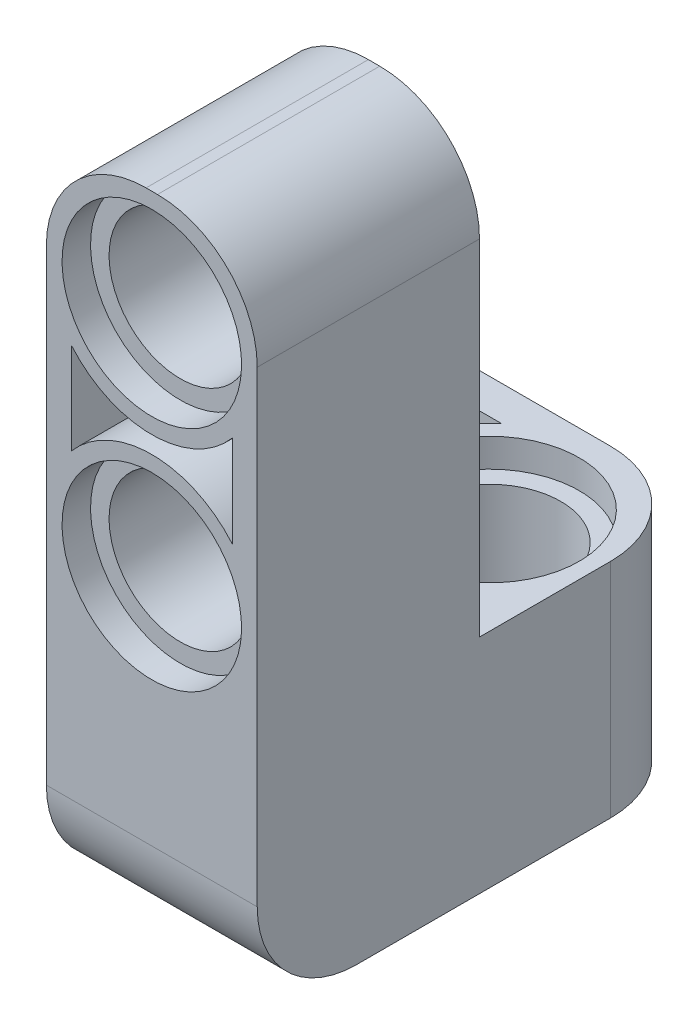
SolidWorks part; units mm, degrees
ref_plane "前视基准面" through (0, 0, 0) normal (0, 0, 1) x (1, 0, 0)
ref_plane "上视基准面" through (0, 0, 0) normal (0, 1, 0) x (1, 0, 0)
ref_plane "右视基准面" through (0, 0, 0) normal (1, 0, 0) x (0, 0, -1)
other "Configuration Table"
sketch "草图3" plane through (0, 0, 0) normal (1, 0, 0) x (0, 0, -1)
  line L0 (-4.1, 0) -> (-4, 0)
  line L5 (-4, 7.8) -> (4, 7.8)
  line L6 (-4, 7.8) -> (-4, 0)
  line L7 (-4, 0) -> (4, 0)
  line L8 (4, 7.8) -> (4, 0)
  line L13 (-11.9, 23.4) -> (-4.1, 23.4)
  line L14 (-11.9, 23.4) -> (-11.9, 0)
  line L15 (-11.9, 0) -> (-4.1, 0)
  line L16 (-4.1, 23.4) -> (-4.1, 0)
  line L21 (-4, 7.8) -> (-4.1, 7.8)
  line L22 (4, 7.8) -> (4.1, 7.8)
  line L23 (4, 0) -> (4.1, 0)
  line L24 (-8, 23.4) -> (-8, 0) construction
  line L26 (0, 7.8) -> (0, 0) construction
  dimension "D1" = 8
  dimension "D2" = 7.8
  dimension "D3" = 7.8
  dimension "D4" = 8
  dimension "D5" = 23.4
extrude "凸台-拉伸1" add sketch "草图3" along normal blind 7.4 contours L16 L13 L14 L15 | L8 L5 L6 L7 | L6 L21 L16 L0 | L8 L23 L22 region at (0, 3.9, 4.05) region at (0, 11.7, 8) region at (0, 3.9, 0)
sketch "草图4" plane through (0, 7.8, 0) normal (0, 1, 0) x (1, 0, 0)
  line L0 (3.7, 4) -> (3.7, -4.1) construction
  line L2 (7.4, -4.1) -> (0, -4.1) construction
  line L3 (0, 0) -> (7.4, 0) construction
  line L5 (7.4, 4) -> (0, 4) construction
  circle A0 centre (3.7, -0.05) radius 2.5
  circle A1 centre (3.7, -0.05) radius 3.15
  circle A2 centre (3.7, -0.05) radius 3.7
  point P2 (0, 0)
  point P9 (0, 0)
  point P15 (0, 0)
  dimension "D1" = 7.4
  dimension "D2" = 6.3
  dimension "D3" = 5
extrude "切除-拉伸1" cut sketch "草图4" against normal up to next contours A0 region at (3.7, 7.8, 0.05)
extrude "切除-拉伸2" cut sketch "草图4<3>" against normal blind 1 contours A1 A0 region at (0.6391, 7.8, 0.05)
sketch "草图4<3>" plane through (0, 7.8, 0) normal (0, 1, 0) x (1, 0, 0) same geometry as "草图4"
extrude "切除-拉伸3" cut sketch "草图4<4>" along normal blind 1 from surface contours A1 A0 region at (0.6391, 7.8, 0.05) starting at face at (3.7, 0, 2.55)
sketch "草图4<4>" plane through (0, 7.8, 0) normal (0, 1, 0) x (1, 0, 0) same geometry as "草图4"
sketch "草图5" plane through (0, 0, 4.1) normal (0, 0, -1) x (-1, 0, 0)
  line L0 (-3.7, 23.4) -> (-3.7, 0) construction
  line L1 (-7.4, 0) -> (0, 0) construction
  line L3 (-7.4, 11.7) -> (0, 11.7) construction
  line L6 (-7.4, 23.4) -> (0, 23.4) construction
  line L7 (-7.4, 3.9) -> (0, 3.9) construction
  line L8 (-7.4, 7.8) -> (-7.4, 0) construction
  line L9 (0, 7.8) -> (0, 0) construction
  circle A0 centre (-3.7, 11.7) radius 2.5
  circle A1 centre (-3.7, 11.7) radius 3.15
  circle A2 centre (-3.7, 11.7) radius 3.7
  point P2 (0, 0)
  dimension "D1" = 7.4
  dimension "D2" = 6.3
  dimension "D3" = 5
  dimension "D4" = 7.8
extrude "切除-拉伸4" cut sketch "草图5" against normal through all contours A0 region at (3.7, 11.7, 4.1)
extrude "切除-拉伸5" cut sketch "草图5<3>" against normal blind 1 contours A1 A0 region at (6.7609, 11.7, 4.1)
sketch "草图5<3>" plane through (0, 0, 4.1) normal (0, 0, -1) x (-1, 0, 0) same geometry as "草图5"
extrude "切除-拉伸6" cut sketch "草图5<4>" along normal blind 1 from surface contours A1 A0 region at (6.7609, 11.7, 4.1) starting at face at (3.7, 14.2, 11.9)
sketch "草图5<4>" plane through (0, 0, 4.1) normal (0, 0, -1) x (-1, 0, 0) same geometry as "草图5"
sketch "草图6" plane through (0, 0, 4.1) normal (0, 0, -1) x (-1, 0, 0)
  line L0 (-3.7, 23.4) -> (-3.7, 0) construction
  line L3 (-7.4, 11.7) -> (0, 11.7) construction
  line L6 (-1.2, 11.7) -> (-0.55, 11.7)
  line L7 (-6.85, 11.7) -> (-6.2, 11.7)
  line L8 (-6.525, 11.7) -> (-6.525, 17.3106)
  line L9 (-0.875, 11.7) -> (-0.875, 17.3106)
  line L10 (-7.4, 23.4) -> (0, 23.4) construction
  line L11 (-7.4, 23.4) -> (-7.4, 7.8) construction
  line L12 (-7.4, 23.4) -> (-7.4, 0)
  line L13 (-7.4, 7.8) -> (-7.4, 0) construction
  line L14 (-7.4, 0) -> (0, 0) construction
  line L15 (0, 23.4) -> (0, 7.8) construction
  circle A0 centre (-3.7, 11.7) radius 2.5
  circle A1 centre (-3.7, 11.7) radius 3.15
  circle A2 centre (-3.7, 11.7) radius 3.7
  circle A3 centre (-3.7, 19.7) radius 3.7
  point P2 (0, 0)
  point P8 (0, 0)
  dimension "D1" = 7.4
  dimension "D2" = 6.3
  dimension "D3" = 5
  dimension "D4" = 7.4
  dimension "D5" = 8
extrude "切除-拉伸9" cut sketch "草图6" against normal blind 2 contours A3 L8 A2 L9 region at (3.7, 15.7, 4.1)
extrude "切除-拉伸10" cut sketch "草图6<3>" along normal blind 2 from surface contours A3 L8 A2 L9 region at (3.7, 15.7, 4.1) starting at face at (3.7, 11.7, 11.9)
sketch "草图6<3>" plane through (0, 0, 4.1) normal (0, 0, -1) x (-1, 0, 0) same geometry as "草图6"
pattern_linear "阵列(线性)1" count 2 spacing 8 along (0, 1, 0) of "切除-拉伸4", "切除-拉伸5", "切除-拉伸6"
sketch "草图7" plane through (0, 0, 0) normal (1, 0, 0) x (0, 0, -1)
  line L0 (-11.9, 0) -> (4, 0) construction
  line L1 (4, 7.8) -> (-3.95, 7.8)
  line L2 (4, 7.8) -> (4, 0)
  line L3 (4, 0) -> (-3.95, 0)
  line L4 (-3.95, 7.8) -> (-3.95, 0)
extrude "凸台-拉伸2" add sketch "草图7" against normal blind 7.8
pattern_linear "阵列(线性)2" count 2 spacing 8 along (-1, 0, 0) of "切除-拉伸1", "切除-拉伸2", "切除-拉伸3"
sketch "草图9" plane through (0, 0, 0) normal (0, -1, 0) x (1, 0, 0)
  line L0 (3.7, 11.9) -> (3.7, -4) construction
  line L1 (7.4, 11.9) -> (0, 11.9) construction
  line L2 (7.4, -4) -> (-7.8, -4) construction
  line L3 (-7.8, 0.05) -> (7.4, 0.05)
  line L6 (3.7, 3.2) -> (3.7, 2.55)
  line L7 (3.7, -3.1) -> (3.7, -2.45)
  line L8 (3.7, -2.775) -> (-1.9106, -2.775)
  line L9 (3.7, 2.875) -> (-1.9106, 2.875)
  circle A0 centre (3.7, 0.05) radius 2.5
  circle A1 centre (3.7, 0.05) radius 3.15
  circle A2 centre (3.7, 0.05) radius 3.7
  circle A3 centre (-4.3, 0.05) radius 3.7
  point P12 (-4.3, 0.05)
  point P17 (3.7, 0.05)
  dimension "D1" = 7.4
  dimension "D2" = 6.3
  dimension "D3" = 5
  dimension "D4" = 7.4
extrude "切除-拉伸11" cut sketch "草图9" against normal blind 2 contours A3 L3 A2 L9 | A3 L8 A2 L3 region at (-0.3, 0, 1.8819) region at (-0.3, 0, -1.7819)
extrude "切除-拉伸12" cut sketch "草图9<3>" along normal blind 2 from surface contours A3 L3 A2 L9 | A3 L8 A2 L3 region at (-0.3, 0, 1.8819) region at (-0.3, 0, -1.7819) starting at face at (-4.3, 7.8, 3.2)
sketch "草图9<3>" plane through (0, 0, 0) normal (0, -1, 0) x (1, 0, 0) same geometry as "草图9"
fillet "圆角1" radius 3.5 6 edges at (3.7, 0, 11.9) (7.4, 3.9, -4) (-7.8, 3.9, -4) (-7.8, 3.9, 3.95) (7.4, 23.4, 8) (0, 23.4, 8)
